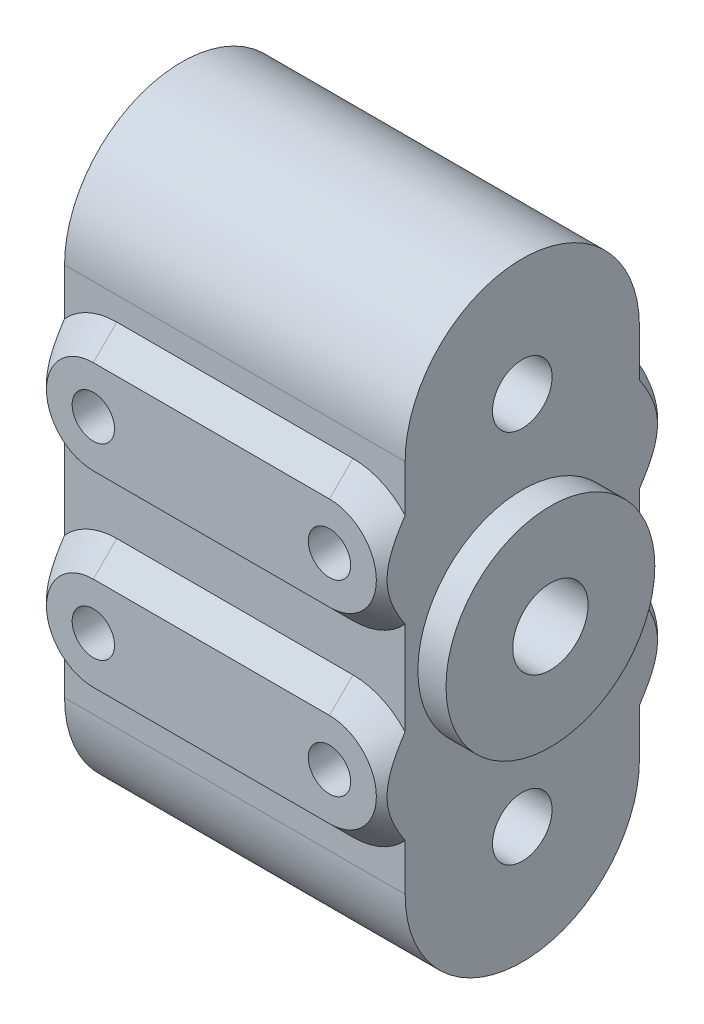
SolidWorks part; units mm, degrees
material "PET"
ref_plane "Front" through (0, 0, 0) normal (0, 0, 1) x (1, 0, 0)
ref_plane "Top" through (0, 0, 0) normal (0, 1, 0) x (1, 0, 0)
ref_plane "Right" through (0, 0, 0) normal (1, 0, 0) x (0, 0, -1)
sketch "Sketch1" plane through (0, 0, 0) normal (1, 0, 0) x (0, 0, -1)
  line L0 (0, 12.7) -> (0, -12.7) construction
  line L1 (7.9375, 12.7) -> (7.9375, -12.7)
  line L2 (-7.9375, 12.7) -> (-7.9375, -12.7)
  arc A0 (7.9375, 12.7) -> (-7.9375, 12.7) centre (0, 12.7) ccw
  arc A1 (-7.9375, -12.7) -> (7.9375, -12.7) centre (0, -12.7) ccw
  point P2 (0, 0)
  dimension "D1" = 15.875
  dimension "D2" = 25.4
extrude "Boss-Extrude1" add sketch "Sketch1" along normal blind 23.075
sketch "Sketch8" plane through (23.075, 0, 0) normal (1, 0, 0) x (0, 0, -1)
  circle A0 centre (0, 0) radius 7.0739
  dimension "D1" = 14.1478
extrude "Boss-Extrude2" add sketch "Sketch8" along normal blind 1.905
hole_wizard "1/4-20 Tapped Hole1" positions "Sketch9" profile "Sketch10" tap size "1/4-20" standard "ANSI Inch" end condition through all
sketch "Sketch9" plane through (24.98, 0, 0) normal (1, 0, 0) x (0, 0, -1)
  point P0 (0, 0)
sketch "Sketch10" plane through (24.98, 0, 0) normal (0, 1, 0) x (0, 0, -1)
  line L0 (0, 0) -> (0, 24.98)
  line L1 (0, 24.98) -> (2.5527, 24.98)
  line L2 (2.5527, 24.98) -> (2.5527, 0)
  line L5 (2.5527, 0) -> (0, 0)
  line L11 (0, -6.35) -> (0, 107.95) construction
  dimension "Thru Tap Drill Dia." = 5.1054
  dimension "Thru Tap Drill Depth" = 24.98
cosmetic thread "Hole Thread8" parameters "D2"=6.35
hole_wizard "#10-32 Tapped Hole1" positions "Sketch4" profile "Sketch5" tap size "#10-32" standard "ANSI Inch" end condition through all
sketch "Sketch4" plane through (23.075, 0, 0) normal (1, 0, 0) x (0, 0, -1)
  point P0 (0, 12.7)
  point P2 (0, -12.7)
sketch "Sketch5" plane through (23.075, 12.7, 0) normal (0, 1, 0) x (0, 0, -1)
  line L0 (0, 0) -> (0, 23.075)
  line L1 (0, 23.075) -> (2.0193, 23.075)
  line L2 (2.0193, 23.075) -> (2.0193, 0)
  line L5 (2.0193, 0) -> (0, 0)
  line L11 (0, -6.35) -> (0, 107.95) construction
  dimension "Thru Tap Drill Dia." = 4.0386
  dimension "Thru Tap Drill Depth" = 23.075
cosmetic thread "Hole Thread2" parameters "D2"=4.826
cosmetic thread "Hole Thread3" parameters "D2"=4.826
ref_plane "Plane1" through (0, 0, 9.525) normal (0, 0, 1) x (1, 0, 0)
sketch "Sketch13" plane through (0, 0, 9.525) normal (0, 0, 1) x (1, 0, 0)
  line L0 (3.5375, 6.35) -> (19.5375, 6.35) construction
  line L1 (3.5375, 9.525) -> (19.5375, 9.525)
  line L2 (3.5375, 3.175) -> (19.5375, 3.175)
  line L3 (0, 0) -> (3.6937, 0) construction
  line L4 (11.5375, 6.35) -> (11.5375, 20.6375) construction
  line L5 (23.075, 20.6375) -> (0, 20.6375) construction
  arc A0 (3.5375, 9.525) -> (3.5375, 3.175) centre (3.5375, 6.35) ccw
  arc A1 (19.5375, 3.175) -> (19.5375, 9.525) centre (19.5375, 6.35) ccw
  point P2 (11.5375, 6.35)
  dimension "D1" = 16
  dimension "D2" = 12.7
  dimension "D3" = 6.35
extrude "Boss-Extrude3" add sketch "Sketch13" against normal blind 2.54 draft 45 draft outward yes
mirror "Mirror1" about plane through (0, 0, 0) normal (0, 1, 0) of "Boss-Extrude3" second plane through (0, 0, 0) second plane normal (0, 0, 1)
sketch "Sketch14" plane through (0, 0, 0) normal (-1, 0, 0) x (0, 0, 1)
  line L1 (-9.525, 20.6375) -> (9.525, 20.6375)
  line L3 (-9.525, 20.6375) -> (-9.525, -20.6375)
  line L6 (-9.525, -20.6375) -> (9.525, -20.6375)
  line L7 (9.525, 20.6375) -> (9.525, -20.6375)
  line L8 (9.525, 3.175) -> (9.525, 9.525) construction
  line L9 (-9.525, 9.525) -> (-9.525, 3.175) construction
  arc A0 (7.9375, 12.7) -> (-7.9375, 12.7) centre (0, 12.7) ccw construction
  arc A1 (-7.9375, -12.7) -> (7.9375, -12.7) centre (0, -12.7) ccw construction
extrude "Cut-Extrude1" cut sketch "Sketch14" along normal through all
sketch "Sketch15" plane through (23.075, 0, 0) normal (1, 0, 0) x (0, 0, -1)
  line L4 (9.525, 20.6375) -> (-9.525, 20.6375)
  line L5 (-9.525, 20.6375) -> (-9.525, -20.6375)
  line L6 (-9.525, -20.6375) -> (9.525, -20.6375)
  line L7 (9.525, -20.6375) -> (9.525, 20.6375)
  line L8 (9.525, 20.6375) -> (-9.525, 20.6375)
  line L9 (-9.525, 20.6375) -> (-9.525, -20.6375)
  line L10 (-9.525, -20.6375) -> (9.525, -20.6375)
  line L11 (9.525, -20.6375) -> (9.525, 20.6375)
  circle A0 centre (0, 0) radius 7.0739 construction
  circle A1 centre (0, 0) radius 7.0739
  dimension "D1" = 0
extrude "Cut-Extrude2" cut sketch "Sketch15" along normal through all
hole_wizard "#6-40 Tapped Hole1" positions "Sketch6" profile "Sketch7" tap size "#6-40" standard "ANSI Inch" end condition through all
sketch "Sketch6" plane through (0, 0, 9.525) normal (0, 0, 1) x (1, 0, 0)
  point P0 (3.5375, 6.35)
  point P2 (19.5375, 6.35)
  point P4 (3.5375, -6.35)
  point P6 (19.5375, -6.35)
  point P71 (0, 0)
  point P72 (0, 0)
  point P73 (19.5375, -6.35)
  point P75 (3.5375, -6.35)
cosmetic thread "Hole Thread4" parameters "D2"=3.5052
cosmetic thread "Hole Thread5" parameters "D2"=3.5052
cosmetic thread "Hole Thread6" parameters "D2"=3.5052
cosmetic thread "Hole Thread7" parameters "D2"=3.5052
sketch "Sketch7" plane through (3.5375, 6.35, 9.525) normal (1, 0, 0) x (0, -1, 0)
  line L0 (0, 0) -> (0, 19.05)
  line L1 (0, 19.05) -> (1.4351, 19.05)
  line L2 (1.4351, 19.05) -> (1.4351, 0)
  line L5 (1.4351, 0) -> (0, 0)
  line L11 (0, -6.35) -> (0, 107.95) construction
  dimension "Thru Tap Drill Dia." = 2.8702
  dimension "Thru Tap Drill Depth" = 19.05
hole_wizard "13/64 (0.20313) Diameter Hole1" positions "Sketch11" profile "Sketch12" hole size "13/64" standard "ANSI Inch"
sketch "Sketch11" plane through (0, 0, 0) normal (-1, 0, 0) x (0, 0, 1)
  point P0 (0, -12.7)
  point P3 (0, 12.7)
sketch "Sketch12" plane through (0, -12.7, 0) normal (0, 1, 0) x (0, 0, 1)
  line L0 (0, 0) -> (0, 4.7251)
  line L1 (0, 4.7251) -> (2.5798, 3.175)
  line L2 (2.5798, 3.175) -> (2.5798, 0)
  line L5 (2.5798, 0) -> (0, 0)
  line L10 (0, 4.7251) -> (-2.5798, 3.175) construction
  line L11 (0, -6.35) -> (0, 107.95) construction
  dimension "Hole Dia." = 5.1595
  dimension "Hole Depth" = 3.175
  dimension "Drill Angle" = 118
